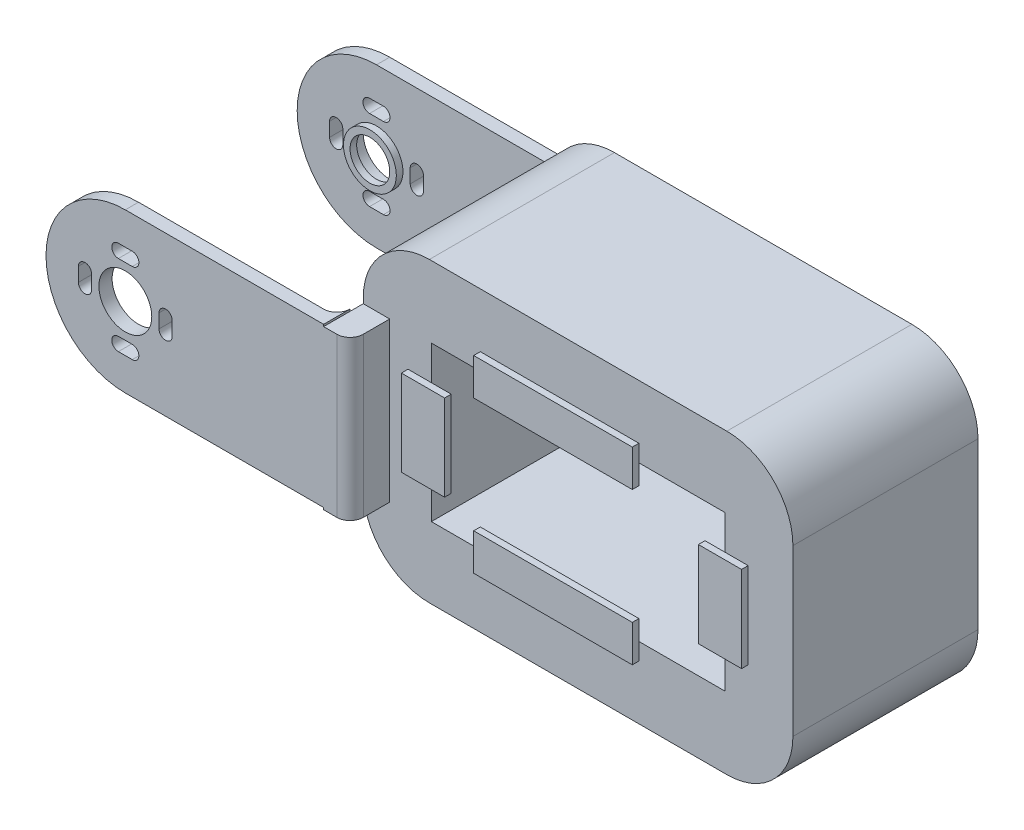
SolidWorks part; units mm, degrees
ref_plane "前基準面" through (0, 0, 0) normal (0, 0, 1) x (1, 0, 0)
ref_plane "上基準面" through (0, 0, 0) normal (0, 1, 0) x (1, 0, 0)
ref_plane "右基準面" through (0, 0, 0) normal (1, 0, 0) x (0, 0, -1)
sketch "草圖1" plane through (0, 0, 0) normal (0, 0, 1) x (1, 0, 0)
  line L0 (-9.02, 0) -> (7.9922, 0) construction
  line L2 (-59.9347, 22.5) -> (5.0653, 22.5)
  line L3 (-59.9347, 22.5) -> (-59.9347, -22.5)
  line L4 (-59.9347, -22.5) -> (5.0653, -22.5)
  line L5 (5.0653, 22.5) -> (5.0653, -22.5)
  dimension "D1" = 45
  dimension "D2" = 22.5
  dimension "D3" = 65
extrude "填料-伸長1" add sketch "草圖1" along normal blind 28
sketch "草圖2" plane through (0, 0, 0) normal (0, 0, 1) x (1, 0, 0)
  line L0 (-59.9347, 0) -> (5.361, 0) construction
  line L1 (-59.9347, 22.5) -> (-59.9347, -22.5) construction
  line L2 (-27.4347, 22.5) -> (-27.4347, -22.5) construction
  line L3 (5.0653, 22.5) -> (-59.9347, 22.5) construction
  line L4 (-59.9347, -22.5) -> (5.0653, -22.5) construction
  line L6 (-49.6347, 11.7) -> (-5.2347, 11.7)
  line L7 (-49.6347, 11.7) -> (-49.6347, -11.7)
  line L8 (-49.6347, -11.7) -> (-5.2347, -11.7)
  line L9 (-5.2347, 11.7) -> (-5.2347, -11.7)
  dimension "D1" = 44.4
  dimension "D2" = 23.4
  dimension "D3" = 10.3
  dimension "D4" = 10.8
extrude "除料-伸長1" cut sketch "草圖2" along normal blind 39
ref_plane "平面1" through (0, 0, 28) normal (0, 0, 1) x (1, 0, 0)
sketch "草圖3" plane through (0, 0, 28) normal (0, 0, 1) x (1, 0, 0)
  line L0 (-59.9347, 22.5) -> (-59.9347, -22.5) construction
  line L2 (-59.9347, 11.7) -> (-55.9347, 11.7)
  line L3 (-59.9347, 11.7) -> (-59.9347, -12.3)
  line L4 (-59.9347, -12.3) -> (-55.9347, -12.3)
  line L5 (-55.9347, 11.7) -> (-55.9347, -12.3)
  line L6 (-49.6347, 11.7) -> (-5.2347, 11.7) construction
  dimension "D1" = 4
  dimension "D2" = 24
  dimension "D3" = 0
extrude "填料-伸長2" add sketch "草圖3" along normal blind 6
ref_plane "平面2" through (-59.9347, 0, 0) normal (-1, 0, 0) x (0, 0, 1)
sketch "草圖4" plane through (-59.9347, 0, 0) normal (-1, 0, 0) x (0, 0, 1)
  line L0 (34, 11.7) -> (28, 11.7) construction
  line L2 (32, 11.7) -> (34, 11.7)
  line L3 (32, 11.7) -> (32, -12.3)
  line L4 (32, -12.3) -> (34, -12.3)
  line L5 (34, 11.7) -> (34, -12.3)
  dimension "D1" = 2
ref_plane "平面3" through (0, 0, 33) normal (0, 0, 1) x (1, 0, 0)
sketch "草圖6" plane through (0, 0, 28) normal (0, 0, 1) x (1, 0, 0)
  line L0 (-15.2347, 0.3) -> (5.0653, -22.5)
  line L1 (-5.2347, 11.7) -> (-5.2347, -11.7) construction
  line L2 (-5.2347, -11.7) -> (-49.6347, -11.7) construction
  line L3 (-15.2347, 0.3) -> (-15.2347, -22.5)
  line L4 (-59.9347, -22.5) -> (5.0653, -22.5) construction
  line L5 (-15.2347, -22.5) -> (5.0653, -22.5)
  dimension "D1" = 10
  dimension "D2" = 12
sketch "草圖7" plane through (0, 0, 33) normal (0, 0, 1) x (1, 0, 0)
  line L0 (-59.9347, 12) -> (-89.9347, 12)
  line L1 (-59.9347, 11.7) -> (-59.9347, -12.3) construction
  line L3 (-59.9347, 0) -> (-109.9347, 0) construction
  line L4 (-59.9347, -12) -> (-89.9347, -12)
  line L5 (-96.0347, 1.05) -> (-96.0347, -1.05) construction
  line L6 (-95.0347, 1.05) -> (-95.0347, -1.05)
  line L7 (-97.0347, 1.05) -> (-97.0347, -1.05)
  line L8 (-90.9847, -6.1) -> (-88.8847, -6.1) construction
  line L9 (-90.9847, -5.1) -> (-88.8847, -5.1)
  line L10 (-90.9847, -7.1) -> (-88.8847, -7.1)
  line L11 (-89.9347, 4) -> (-89.9347, -7.9506) construction
  line L12 (-90.9847, 6.1) -> (-88.8847, 6.1) construction
  line L13 (-90.9847, 5.1) -> (-88.8847, 5.1)
  line L14 (-90.9847, 7.1) -> (-88.8847, 7.1)
  line L15 (-83.8347, 1.05) -> (-83.8347, -1.05) construction
  line L16 (-84.8347, 1.05) -> (-84.8347, -1.05)
  line L17 (-82.8347, 1.05) -> (-82.8347, -1.05)
  line L18 (-59.9347, 12) -> (-59.9347, -12)
  arc A0 (-89.9347, -12) -> (-89.9347, 12) centre (-89.9347, 0) cw
  circle A1 centre (-89.9347, 0) radius 4
  arc A3 (-95.0347, 1.05) -> (-97.0347, 1.05) centre (-96.0347, 1.05) ccw
  arc A4 (-97.0347, -1.05) -> (-95.0347, -1.05) centre (-96.0347, -1.05) ccw
  arc A5 (-90.9847, -5.1) -> (-90.9847, -7.1) centre (-90.9847, -6.1) ccw
  arc A6 (-88.8847, -7.1) -> (-88.8847, -5.1) centre (-88.8847, -6.1) ccw
  arc A7 (-90.9847, 5.1) -> (-90.9847, 7.1) centre (-90.9847, 6.1) cw
  arc A8 (-88.8847, 7.1) -> (-88.8847, 5.1) centre (-88.8847, 6.1) cw
  arc A9 (-84.8347, 1.05) -> (-82.8347, 1.05) centre (-83.8347, 1.05) cw
  arc A10 (-82.8347, -1.05) -> (-84.8347, -1.05) centre (-83.8347, -1.05) cw
  point P15 (-96.0347, 0)
  point P20 (-89.9347, -6.1)
  point P31 (-89.9347, 6.1)
  point P38 (-83.8347, 0)
  dimension "D2" = 8
  dimension "D3" = 50
  dimension "D4" = 6.1
  dimension "D6" = 0
  dimension "D1" = 30
  dimension "D5" = 2.1
  dimension "D7" = 2
  dimension "D8" = 2
  dimension "D9" = 0
  dimension "D10" = 2.1
  dimension "D11" = 6.1
extrude "填料-伸長3" add sketch "草圖7" along normal blind 1 and the other way blind 1
ref_plane "平面4" through (0, 0, 0) normal (0, 0, -1) x (-1, 0, 0)
sketch "草圖8" plane through (0, 0, 0) normal (0, 0, -1) x (-1, 0, 0)
  line L0 (59.9347, 11.7) -> (59.9347, -12.3) construction
  line L1 (55.9347, 12) -> (59.9347, 12)
  line L2 (55.9347, 12) -> (55.9347, -12)
  line L3 (55.9347, -12) -> (59.9347, -12)
  line L4 (59.9347, 12) -> (59.9347, -12)
  dimension "D1" = 24
  dimension "D2" = 4
extrude "填料-伸長4" add sketch "草圖8" along normal blind 6 contours L3 L4 L1 L2
fillet "圓角1" radius 10 1 edges at (-59.9347, -22.5, 14) type face fillet first side face at (-59.9347, -1.8, 16.5714) second side face at (-27.4347, -22.5, 14)
fillet "圓角2" radius 10 1 edges at (-59.9347, 22.5, 14) type face fillet first side face at (-27.4347, 22.5, 14) second side face at (-59.9347, -0.3714, 16.5714)
fillet "圓角3" radius 10 1 edges at (5.0653, 22.5, 14) type face fillet first side face at (-22.4347, 22.5, 14) second side face at (5.0653, 0, 14)
fillet "圓角4" radius 10 1 edges at (5.0653, -22.5, 14) type face fillet first side face at (-22.4347, -22.5, 14) second side face at (5.0653, -5, 14)
pattern_linear "直線複製排列2" count 2 spacing 38 along (0, 0, -1) of "填料-伸長3"
fillet "圓角5" radius 2 1 edges at (-55.9347, 0, -6) type face fillet first side face at (-75.9347, 0, -6) second side face at (-55.9347, 0, -3)
fillet "圓角6" radius 2 1 edges at (-59.9347, 0, -4) type face fillet first side face at (-89.9347, 6.1, -4) second side face at (-59.9347, -1.8, 16.8571)
fillet "圓角7" radius 2 1 edges at (-59.9347, -0.15, 32) type face fillet first side face at (-59.9347, -1.8, 17.1429) second side face at (-83.8347, 0, 32)
fillet "圓角8" radius 2 1 edges at (-55.9347, -0.3, 34) type face fillet first side face at (-67.9347, -0.15, 34) second side face at (-55.9347, -0.3, 31)
ref_plane "平面5" through (0, 0, -4) normal (0, 0, 1) x (1, 0, 0)
sketch "草圖9" plane through (0, 0, -4) normal (0, 0, 1) x (1, 0, 0)
  circle A0 centre (-89.9347, 0) radius 4
  circle A1 centre (-89.9347, 0) radius 3.0041
extrude "填料-伸長5" add sketch "草圖9" along normal blind 1 separate body
ref_plane "平面6" through (0, 0, 29) normal (0, 0, 1) x (1, 0, 0)
sketch "草圖10" plane through (0, 0, 29) normal (0, 0, 1) x (1, 0, 0)
  line L0 (-49.6347, 11.7) -> (-5.2347, 11.7) construction
  line L2 (-42.2347, 11.7) -> (-42.2347, 14.2663)
  line L3 (-42.2347, 14.2663) -> (-18.2347, 14.2663)
  line L4 (-18.2347, 11.7) -> (-18.2347, 14.2663)
  line L5 (-5.2347, 11.7) -> (-5.2347, -11.7) construction
  line L6 (-49.6347, 0) -> (-4.2092, 0) construction
  line L7 (-49.6347, -11.7) -> (-49.6347, 11.7) construction
  line L8 (-27.4347, -11.7) -> (-27.4347, 19.297) construction
  line L9 (-5.2347, -11.7) -> (-49.6347, -11.7) construction
  line L10 (-42.2347, 11.7) -> (-42.2347, 8.7)
  line L11 (-49.6347, 6.5) -> (-53.1651, 6.5)
  line L13 (-49.6347, -6.5) -> (-53.1651, -6.5)
  line L14 (-53.1651, 6.5) -> (-53.1651, -6.5)
  line L15 (-42.2347, 8.7) -> (-18.2347, 8.7)
  line L16 (-18.2347, 8.7) -> (-18.2347, 11.7)
  line L17 (-49.6347, 6.5) -> (-46.6347, 6.5)
  line L18 (-46.6347, 6.5) -> (-46.6347, -6.5)
  line L19 (-46.6347, -6.5) -> (-49.6347, -6.5)
  line L20 (-42.2347, -11.7) -> (-42.2347, -8.7)
  line L21 (-42.2347, -8.7) -> (-18.2347, -8.7)
  line L22 (-18.2347, -8.7) -> (-18.2347, -11.7)
  line L23 (-18.2347, -11.7) -> (-18.2347, -14.2663)
  line L24 (-42.2347, -14.2663) -> (-18.2347, -14.2663)
  line L25 (-42.2347, -11.7) -> (-42.2347, -14.2663)
  line L26 (-5.2347, 6.5) -> (-8.2347, 6.5)
  line L27 (-8.2347, 6.5) -> (-8.2347, -6.5)
  line L28 (-8.2347, -6.5) -> (-5.2347, -6.5)
  line L29 (-5.2347, -6.5) -> (-1.7043, -6.5)
  line L30 (-1.7043, 6.5) -> (-1.7043, -6.5)
  line L31 (-5.2347, 6.5) -> (-1.7043, 6.5)
  point P6 (-18.2347, 12.9831)
  dimension "D1" = 24
  dimension "D2" = 13
  dimension "D3" = 13
  dimension "D4" = 6.5
  dimension "D5" = 3
  dimension "D6" = 3
extrude "填料-伸長6" add sketch "草圖10" against normal blind 1 separate body
